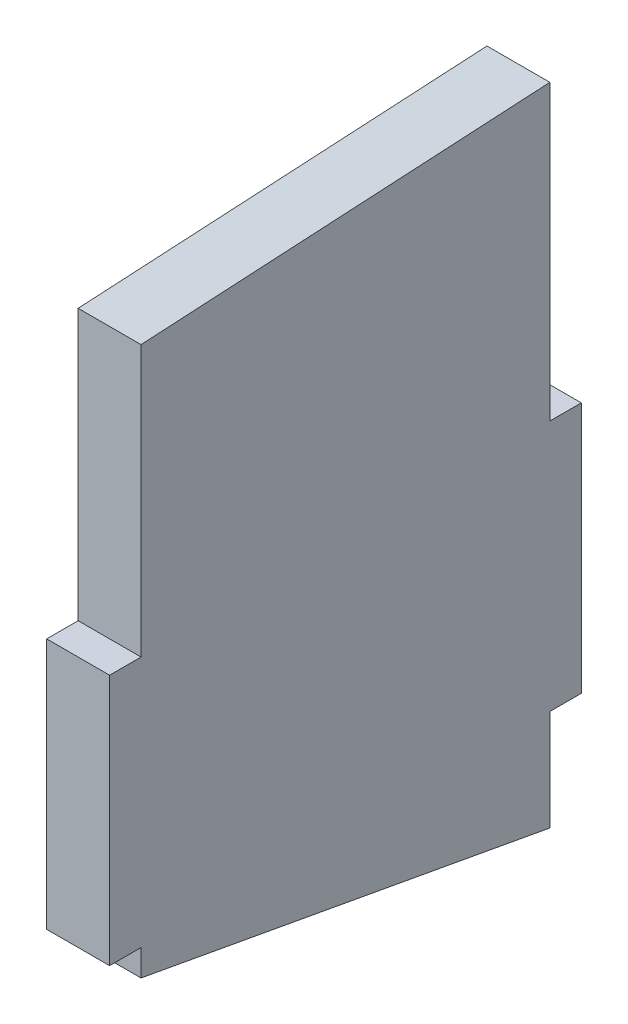
SolidWorks part; units mm, degrees
material "Pink Foam"
ref_plane "Front Plane" through (0, 0, 0) normal (0, 0, 1) x (1, 0, 0)
ref_plane "Top Plane" through (0, 0, 0) normal (0, 1, 0) x (1, 0, 0)
ref_plane "Right Plane" through (0, 0, 0) normal (1, 0, 0) x (0, 0, -1)
sketch "Sketch1" plane through (0, 0, 0) normal (1, 0, 0) x (0, 0, -1)
  line L0 (-82.55, 160.0689) -> (82.55, 169.2558)
  line L1 (-82.55, -203.2) -> (82.55, -203.2)
  line L2 (-82.55, -203.2) -> (-82.55, 203.2)
  line L3 (-82.55, 203.2) -> (82.55, 203.2)
  line L4 (82.55, -203.2) -> (82.55, 203.2)
  line L5 (-82.55, -203.2) -> (82.55, 203.2) construction
  line L6 (-82.55, 203.2) -> (82.55, -203.2) construction
  line L7 (-95.25, -50.8) -> (95.25, -50.8)
  line L8 (-95.25, -50.8) -> (-95.25, 50.8)
  line L9 (-95.25, 50.8) -> (95.25, 50.8)
  line L10 (95.25, -50.8) -> (95.25, 50.8)
  line L11 (-95.25, -50.8) -> (95.25, 50.8) construction
  line L12 (-95.25, 50.8) -> (95.25, -50.8) construction
  line L14 (-82.55, -61.4555) -> (82.55, -91.5455)
  point P0 (0, 0)
  point P6 (0, 0)
  dimension "D1" = 165.1
  dimension "D2" = 190.5
  dimension "D3" = 101.6
  dimension "D4" = 406.4
  dimension "D5" = 43.1311
  dimension "D6" = 33.9442
  dimension "D7" = 111.6545
  dimension "D8" = 221.5244
extrude "Boss-Extrude1" add sketch "Sketch1" along normal blind 25.4 contours L2 L9 L4 L0 | L7 L10 L9 L4 | L9 L2 L7 L4 | L9 L8 L7 L2 | L2 L14 L4 L7 region at (0, 107.7621, -1.1101) region at (0, 0, 0) region at (0, 0, 88.9) region at (0, 0, -88.9) region at (0, -65.1181, -16.1082)
